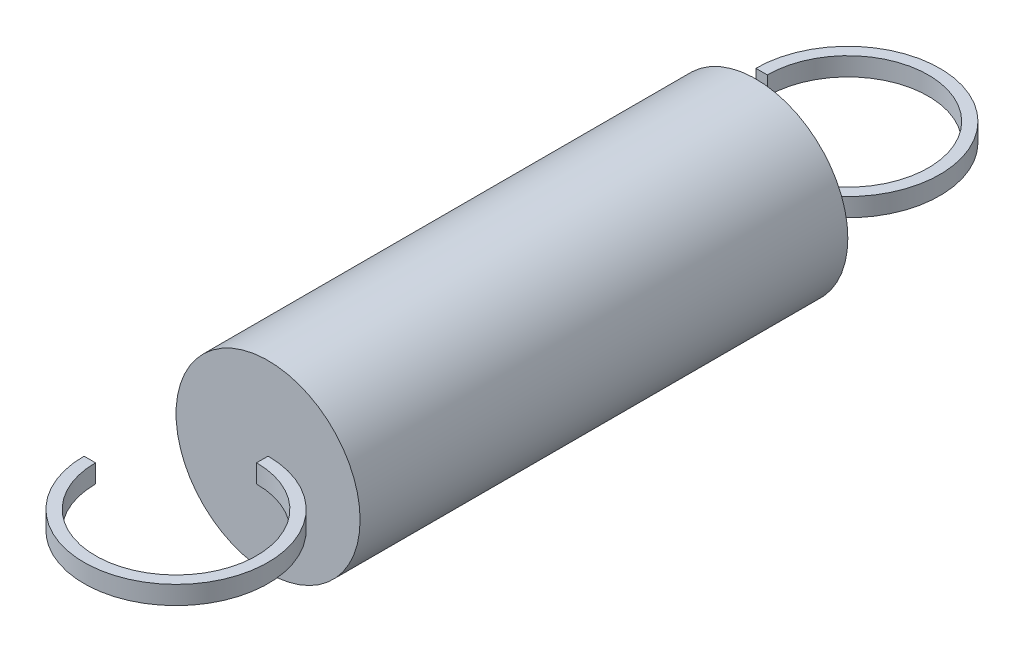
SolidWorks part; units mm, degrees
ref_plane "前视基准面" through (0, 0, 0) normal (0, 0, 1) x (1, 0, 0)
ref_plane "上视基准面" through (0, 0, 0) normal (0, 1, 0) x (1, 0, 0)
ref_plane "右视基准面" through (0, 0, 0) normal (1, 0, 0) x (0, 0, -1)
sketch "草图1" plane through (0, 0, 0) normal (0, 0, 1) x (1, 0, 0)
  circle A0 centre (0, 0) radius 10
  dimension "D1" = 20
extrude "凸台-拉伸1" add sketch "草图1" along normal blind 53
sketch "草图5" plane through (0, 0, 0) normal (0, 1, 0) x (1, 0, 0)
  line L0 (-10, -53) -> (10, -53) construction
  line L1 (-10, -63) -> (-8.75, -63)
  line L2 (0, -54.25) -> (0, -53)
  line L3 (-10, -26.5) -> (9.6824, -26.5) construction
  line L4 (-10, 0) -> (-10, -53) construction
  line L5 (0, 1.25) -> (0, 0)
  line L6 (-10, 10) -> (-8.75, 10)
  circle A1 centre (0, -63) radius 10 construction
  circle A3 centre (0, -63) radius 8.75 construction
  arc A4 (-10, -63) -> (0, -53) centre (0, -63) ccw
  arc A5 (-8.75, -63) -> (0, -54.25) centre (0, -63) ccw
  circle A6 centre (0, 10) radius 8.75 construction
  circle A7 centre (0, 10) radius 10 construction
  arc A8 (-8.75, 10) -> (0, 1.25) centre (0, 10) cw
  arc A9 (-10, 10) -> (0, 0) centre (0, 10) cw
  point P2 (0, 0)
  dimension "D2" = 20
  dimension "D4" = 17.5
extrude "凸台-拉伸2" add sketch "草图5" along normal blind 1 and the other way blind 1 separate body
ref_point "点1"
ref_point "点2"
ref_axis "基准轴1" through (0, -1, 63) along (0, 0, -1)
